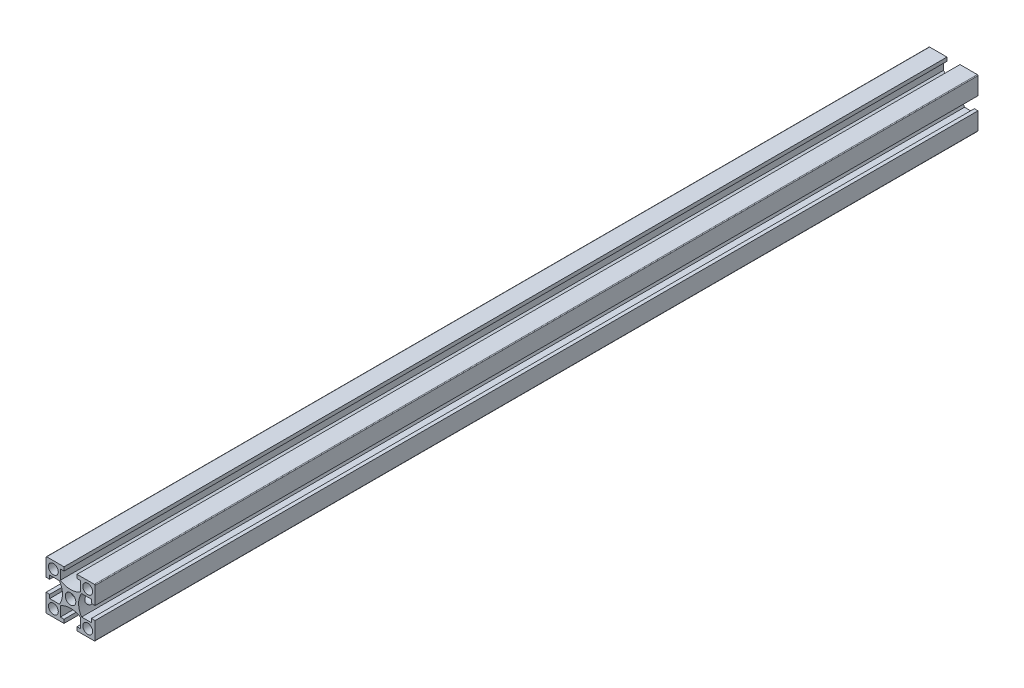
SolidWorks part; units mm, degrees
ref_plane "정면" through (0, 0, 0) normal (0, 0, 1) x (1, 0, 0)
ref_plane "윗면" through (0, 0, 0) normal (0, 1, 0) x (1, 0, 0)
ref_plane "우측면" through (0, 0, 0) normal (1, 0, 0) x (0, 0, -1)
sketch "스케치1" plane through (0, 0, 0) normal (0, 0, 1) x (1, 0, 0)
  line L0 (0, 32.0265) -> (0, -31.6588) construction
  line L1 (-10, 10) -> (-10, -10)
  line L2 (-10, 10) -> (10, 10)
  line L3 (-10, 2.65) -> (-8.5, 2.65)
  line L4 (13.6618, 0) -> (-11.6993, 0) construction
  line L5 (-8.5, 2.65) -> (-8.5, 4.15)
  line L6 (-8.5, 4.15) -> (-4.5032, 4.15)
  line L7 (-10, -2.65) -> (-8.5, -2.65)
  line L8 (-8.5, -2.65) -> (-8.5, -4.15)
  line L9 (-8.5, -4.15) -> (-4.5032, -4.15)
  line L10 (-10, -10) -> (10, -10)
  line L11 (10, 10) -> (10, -10)
  circle A0 centre (-7, 7) radius 2
  circle A1 centre (-7, -7) radius 2
  arc A2 (-4.5032, 4.15) -> (-4.5032, -4.15) centre (-11.0587, 0) cw
  circle A3 centre (0, 0) radius 2.15
  circle A4 centre (7, 7) radius 2
  circle A5 centre (7, -7) radius 2
  point P21 (-10, 0)
  point P23 (-3.3, 0)
  point P31 (0, -10)
  point P32 (0, 10)
  dimension "D3" = 4
  dimension "D9" = 6.7
  dimension "D10" = 4.3
  dimension "D11" = 7.7587
  dimension "D1" = 20
  dimension "D2" = 20
  dimension "D4" = 14
  dimension "D5" = 14
  dimension "D6" = 5.3
  dimension "D7" = 8.3
  dimension "D8" = 1.5
extrude "보스-돌출1" add sketch "스케치1" along normal blind 360 contours A0 | A4 | A3 | A5 | A1 | A2 L6 L5 L3 L1 L7 L8 L9 | L2 L11 L10 L1 region at (-6.6069, 0, 0) region at (-7, 7, 0) region at (-7, -7, 0) region at (0, 0, 0) region at (7, 7, 0) region at (7, -7, 0)
extrude "컷-돌출1" cut sketch "스케치1<3>" along normal up to next contours A2 L6 L5 L3 L1 L7 L8 L9 region at (-6.6069, 0, 0)
sketch "스케치1<3>" plane through (0, 0, 0) normal (0, 0, 1) x (1, 0, 0) same geometry as "스케치1"
pattern_circular "원형 패턴1" count 4 over 360 about axis through (0, 0, 360) along (0, 0, -1) of "컷-돌출1" reverse direction yes
fillet "필렛1" radius 0.3 4 edges at (10, -10, 180) (-10, -10, 180) (-10, 10, 180) (10, 10, 180)
sketch "스케치2" plane through (0, 0, 0) normal (1, 0, 0) x (0, 0, -1)
  line L0 (0, -2.65) -> (0, -9.7) construction
  line L1 (-360, 4.15) -> (-360, -4.15) construction
  circle A0 centre (-5, 0) radius 2.5
  circle A1 centre (-355, 0) radius 2.5
  point P9 (0, 0)
  point P10 (0, 0)
  point P11 (0, 0)
  dimension "D1" = 5
  dimension "D4" = 5
  dimension "D2" = 5
  dimension "D3" = 5
extrude "컷-돌출2" cut sketch "스케치2" against normal through all both and the other way through all contours A0 | A1
